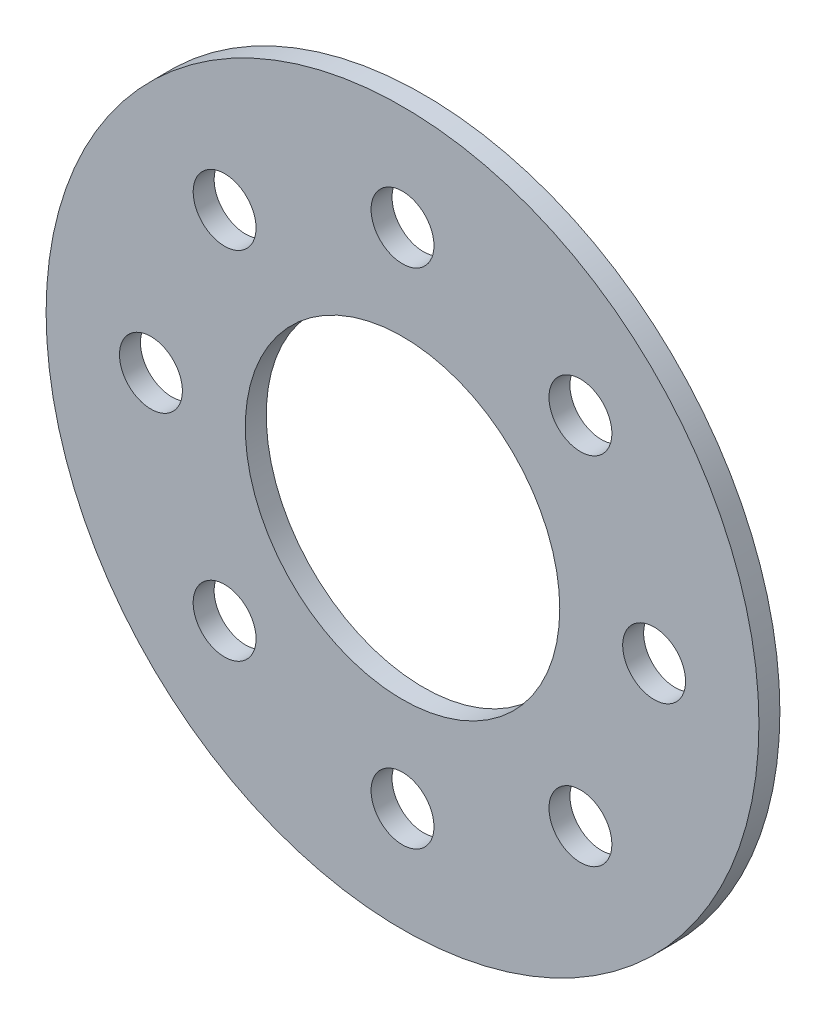
SolidWorks part; units mm, degrees
material "PLA 50%"
ref_plane "Front Plane" through (0, 0, 0) normal (0, 0, 1) x (1, 0, 0)
ref_plane "Top Plane" through (0, 0, 0) normal (0, 1, 0) x (1, 0, 0)
ref_plane "Right Plane" through (0, 0, 0) normal (1, 0, 0) x (0, 0, -1)
ref_axis "X" through (-88.99, 0, 0) along (1, 0, 0)
ref_axis "Y" through (0, 55, 0) along (0, -1, 0)
ref_axis "Z" through (0, 0, -88.99) along (0, 0, 1)
sketch "Sketch1" plane through (0, 0, 0) normal (0, 0, 1) x (1, 0, 0)
  circle A0 centre (0, 0) radius 7.5
  circle A1 centre (0, 0) radius 17
  dimension "D1" = 34
  dimension "D2" = 15
extrude "Boss-Extrude1" add sketch "Sketch1" along normal blind 1
sketch "Sketch2" plane through (0, 0, 1) normal (0, 0, 1) x (1, 0, 0)
  circle A0 centre (0, 12) radius 1.5
  dimension "D1" = 3
  dimension "D2" = 12
extrude "Cut-Extrude1" cut sketch "Sketch2" against normal through all both
pattern_circular "CirPattern1" count 8 over 360 about axis through (0, 0, 1) along (0, 0, -1) of "Cut-Extrude1"
